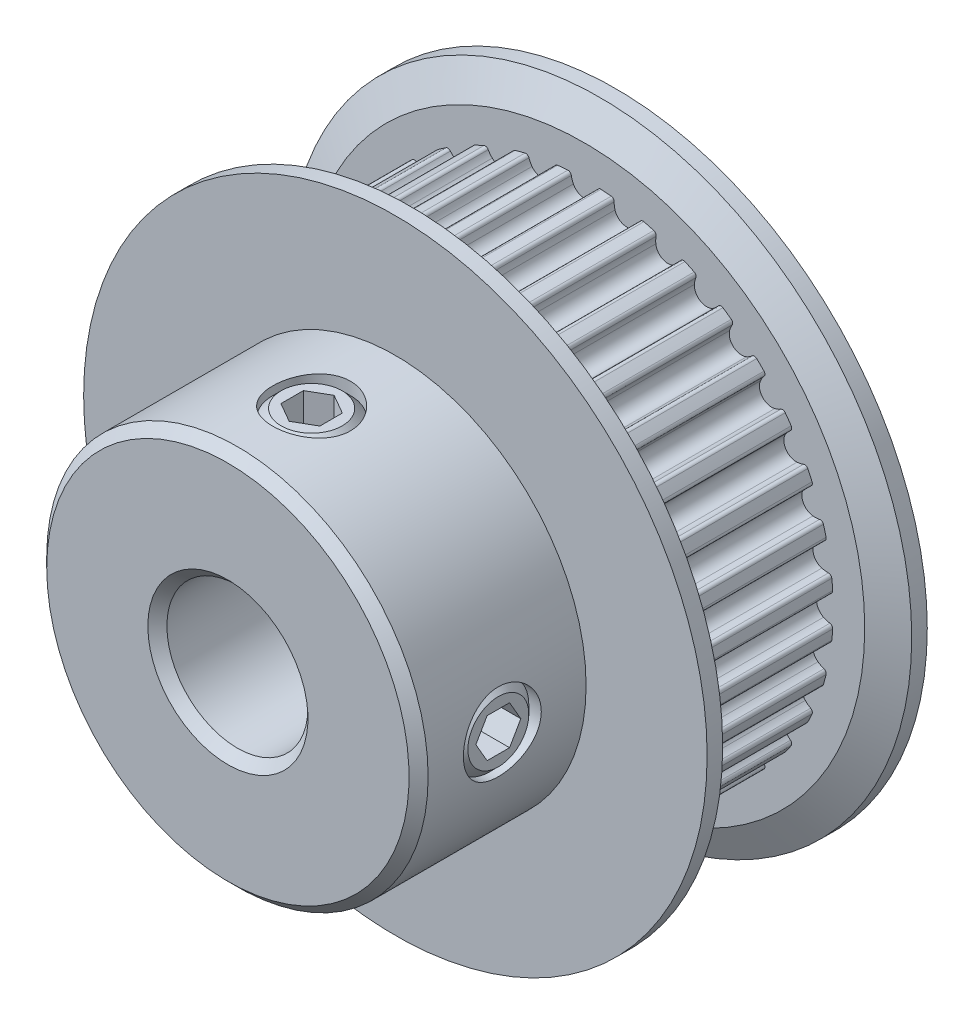
SolidWorks part; units mm, degrees
ref_plane "Front Plane" through (0, 0, 0) normal (0, 0, 1) x (1, 0, 0)
ref_plane "Top Plane" through (0, 0, 0) normal (0, 1, 0) x (1, 0, 0)
ref_plane "Right Plane" through (0, 0, 0) normal (1, 0, 0) x (0, 0, -1)
sketch "Sketch1" plane through (0, 0, 0) normal (0, 0, 1) x (1, 0, 0)
  line L1 (-1.8459, 10.4515) -> (1.8459, 10.4515) construction
  line L4 (0, 0) -> (0, 10.4515) construction
  line L5 (0, 10.4515) -> (0, 14.8978) construction
  line L6 (0, 11.4555) -> (1.9924, 11.2809) construction
  line L7 (1.9924, 11.2809) -> (2.8218, 11.1344) construction
  line L8 (1.9924, 11.2809) -> (1.8459, 10.4515) construction
  line L9 (-1.9924, 11.2809) -> (-1.8459, 10.4515) construction
  line L10 (-1.9482, 11.0308) -> (-2.4785, 14.0335)
  line L11 (-2.4785, 14.0335) -> (2.4785, 14.0335)
  line L12 (2.4785, 14.0335) -> (1.9482, 11.0308)
  circle A0 centre (0, 0) radius 11.4555 construction
  circle A1 centre (0, 0) radius 14.0335 construction
  circle A2 centre (0, 0) radius 11.2015 construction
  arc A3 (-0.4989, 10.7633) -> (0.4989, 10.7633) centre (0, 11.0065) ccw
  arc A4 (-0.4989, 10.7633) -> (-0.5884, 11.0497) centre (0.4, 11.2015) cw
  arc A5 (-1.9482, 11.0308) -> (-0.7467, 11.1766) centre (0, 0) cw
  arc A6 (-0.5884, 11.0497) -> (-0.7467, 11.1766) centre (-0.7367, 11.0269) ccw
  arc A7 (1.9482, 11.0308) -> (0.7467, 11.1766) centre (0, 0) ccw
  arc A8 (0.5884, 11.0497) -> (0.7467, 11.1766) centre (0.7367, 11.0269) cw
  arc A9 (0.4989, 10.7633) -> (0.5884, 11.0497) centre (-0.4, 11.2015) ccw
  point P6 (0, 20.9083)
  point P11 (0, 11.4555)
  point P13 (0, 14.0335)
  point P14 (0, 11.2015)
  dimension "D1" = 6.0106
  dimension "D2" = 3.4423
sketch "Sketch2" plane through (0, 0, 0) normal (1, 0, 0) x (0, 0, -1)
  line L0 (-8.7249, 3.175) -> (8.7249, 3.175)
  line L1 (-8.7249, 3.175) -> (-8.7249, 8.585)
  line L2 (-8.7249, 8.585) -> (-1.1851, 8.585)
  line L3 (-1.1851, 8.585) -> (-1.1851, 14.0335)
  line L4 (-1.1851, 14.0335) -> (0.2149, 14.0335) construction
  line L5 (0.2149, 14.0335) -> (0.2149, 11.2015) construction
  line L6 (0.2149, 11.2015) -> (7.3249, 11.2015)
  line L7 (7.3249, 11.2015) -> (7.3249, 14.0335) construction
  line L8 (7.3249, 14.0335) -> (8.7249, 14.0335) construction
  line L9 (8.7249, 14.0335) -> (8.7249, 3.175)
  line L10 (-8.7249, 0) -> (8.7249, 0) construction
  line L11 (8.0249, 14.0335) -> (7.3249, 12.6175)
  line L12 (0.2149, 12.6175) -> (-0.4851, 14.0335)
  line L13 (-1.1851, 14.0335) -> (-0.4851, 14.0335)
  line L14 (0.2149, 12.6175) -> (0.2149, 11.2015)
  line L15 (7.3249, 11.2015) -> (7.3249, 12.6175)
  line L16 (8.0249, 14.0335) -> (8.7249, 14.0335)
  arc A0 (0.2149, 12.6175) -> (-0.4851, 14.0335) centre (-1.5673, 12.6175) ccw construction
  arc A1 (7.3249, 12.6175) -> (8.0249, 14.0335) centre (9.1071, 12.6175) cw construction
  point P12 (0.2149, 12.6175)
  point P14 (-0.4851, 14.0335)
  point P20 (7.3249, 12.6175)
  point P21 (8.0249, 14.0335)
  point P25 (7.3249, 0)
  point P26 (0.2149, 0)
revolve "Revolve1" add sketch "Sketch2" angle 360 mid plane about L10
sketch "Sketch3" plane through (0, 0, 0) normal (0, 0, 1) x (1, 0, 0)
  line L6 (2.4785, 14.0335) -> (-2.4785, 14.0335)
  line L7 (1.9482, 11.0308) -> (2.4785, 14.0335)
  line L8 (-2.4785, 14.0335) -> (-1.9482, 11.0308)
  line L9 (2.4785, 14.0335) -> (-2.4785, 14.0335)
  line L10 (1.9482, 11.0308) -> (2.4785, 14.0335)
  line L11 (-2.4785, 14.0335) -> (-1.9482, 11.0308)
  arc A8 (1.9482, 11.0308) -> (0.7467, 11.1766) centre (0, 0) ccw
  arc A9 (0.7467, 11.1766) -> (0.5884, 11.0497) centre (0.7367, 11.0269) ccw
  arc A10 (0.4989, 10.7633) -> (0.5884, 11.0497) centre (-0.4, 11.2015) ccw
  arc A11 (-0.4989, 10.7633) -> (0.4989, 10.7633) centre (0, 11.0065) ccw
  arc A12 (-0.5884, 11.0497) -> (-0.4989, 10.7633) centre (0.4, 11.2015) ccw
  arc A13 (-0.5884, 11.0497) -> (-0.7467, 11.1766) centre (-0.7367, 11.0269) ccw
  arc A14 (-0.7467, 11.1766) -> (-1.9482, 11.0308) centre (0, 0) ccw
  arc A15 (1.9482, 11.0308) -> (0.7467, 11.1766) centre (0, 0) ccw
  arc A16 (0.7467, 11.1766) -> (0.5884, 11.0497) centre (0.7367, 11.0269) ccw
  arc A17 (0.4989, 10.7633) -> (0.5884, 11.0497) centre (-0.4, 11.2015) ccw
  arc A18 (-0.4989, 10.7633) -> (0.4989, 10.7633) centre (0, 11.0065) ccw
  arc A19 (-0.5884, 11.0497) -> (-0.4989, 10.7633) centre (0.4, 11.2015) ccw
  arc A20 (-0.5884, 11.0497) -> (-0.7467, 11.1766) centre (-0.7367, 11.0269) ccw
  arc A21 (-0.7467, 11.1766) -> (-1.9482, 11.0308) centre (0, 0) ccw
  dimension "D1" = 0
extrude "Cut-Extrude1" cut sketch "Sketch3" against normal up to vertex (7.3249 mm away) from vertex up to point (0, 11.2015, -7.3249) starting at point (0, 11.2015, -0.2149)
pattern_circular "CirPattern1" count 36 over 360 about axis through (0, 0, 8.7249) along (0, 0, 1) of "Cut-Extrude1"
sketch "Sketch4" plane through (0, 0, 0) normal (1, 0, 0) x (0, -1, 0)
  line L0 (0, -1.1851) -> (0, -8.7249) construction
  line L1 (-8.585, -1.1851) -> (8.585, -1.1851) construction
  line L2 (-8.585, -8.7249) -> (8.585, -8.7249) construction
  circle A0 centre (0, -4.955) radius 1.7526
extrude "Cut-Extrude2" cut sketch "Sketch4" along normal through all
ref_plane "Plane1" through (0, 0, 4.955) normal (0, 0, 1) x (1, 0, 0)
sketch "Sketch5" plane through (0, 0, 4.955) normal (0, 0, 1) x (1, 0, 0)
  line L0 (0, 0.1664) -> (0, 8.585) construction
  line L1 (3.175, -1.3716) -> (3.175, 0)
  line L2 (3.556, -1.7526) -> (8.0232, -1.7526)
  line L3 (3.175, 0) -> (8.585, 0) construction
  line L4 (3.175, 0) -> (8.4042, 0)
  line L5 (8.4042, 0) -> (8.4042, -1.3716)
  line L6 (3.556, -1.7526) -> (3.175, -1.3716)
  line L7 (8.4042, -1.3716) -> (8.0232, -1.7526)
  circle A0 centre (0, 0) radius 8.585 construction
  circle A1 centre (0, 0) radius 3.175 construction
  point P2 (3.175, -1.7526)
  point P11 (8.4042, -1.7526)
revolve "Revolve2" add sketch "Sketch5" angle 360 mid plane about L4
sketch "Sketch6" plane through (8.4042, 5.3841, 0) normal (-1, 0, 0) x (0, -1, 0)
  line L1 (5.3841, 5.9669) -> (4.5078, 5.4609)
  line L2 (4.5078, 5.4609) -> (4.5078, 4.4491)
  line L3 (4.5078, 4.4491) -> (5.3841, 3.9431)
  line L4 (5.3841, 3.9431) -> (6.2604, 4.4491)
  line L5 (6.2604, 4.4491) -> (6.2604, 5.4609)
  line L6 (6.2604, 5.4609) -> (5.3841, 5.9669)
  circle A0 centre (5.3841, 4.955) radius 0.8763 construction
  dimension "D1" = 1.7526
extrude "Cut-Extrude3" cut sketch "Sketch6" along normal blind 1.3144
pattern_circular "CirPattern2" count 2 over 90 about axis through (0, 0, 8.7249) along (0, 0, 1) of "Cut-Extrude2", "Revolve2", "Cut-Extrude3"
chamfer "Chamfer1" distance 0.4293 angle 45 2 edges at (3.175, 0, 8.7249) (8.585, 0, 8.7249)
ref_axis "Center Axis 1" through (0, 0, -8.7249) along (0, 0, 1)
ref_plane "Contact Plane 1" through (0, 0, 8.7249) normal (0, 0, 1) x (1, 0, 0)
ref_plane "Contact Plane 2" through (0, 0, -8.7249) normal (0, 0, -1) x (-1, 0, 0)
equation "\"D2@Sketch1\" = \"D1@Sketch1\"/2"
equation "\"D1@Sketch6\" = \"Set Screw@Sketch4\" / 2"
equation "\"D1@Cut-Extrude3\" = \"D1@Sketch6\"*.75"
equation "\"D1@Chamfer1\"=\"Hub Dia@Sketch2\"*.025"
